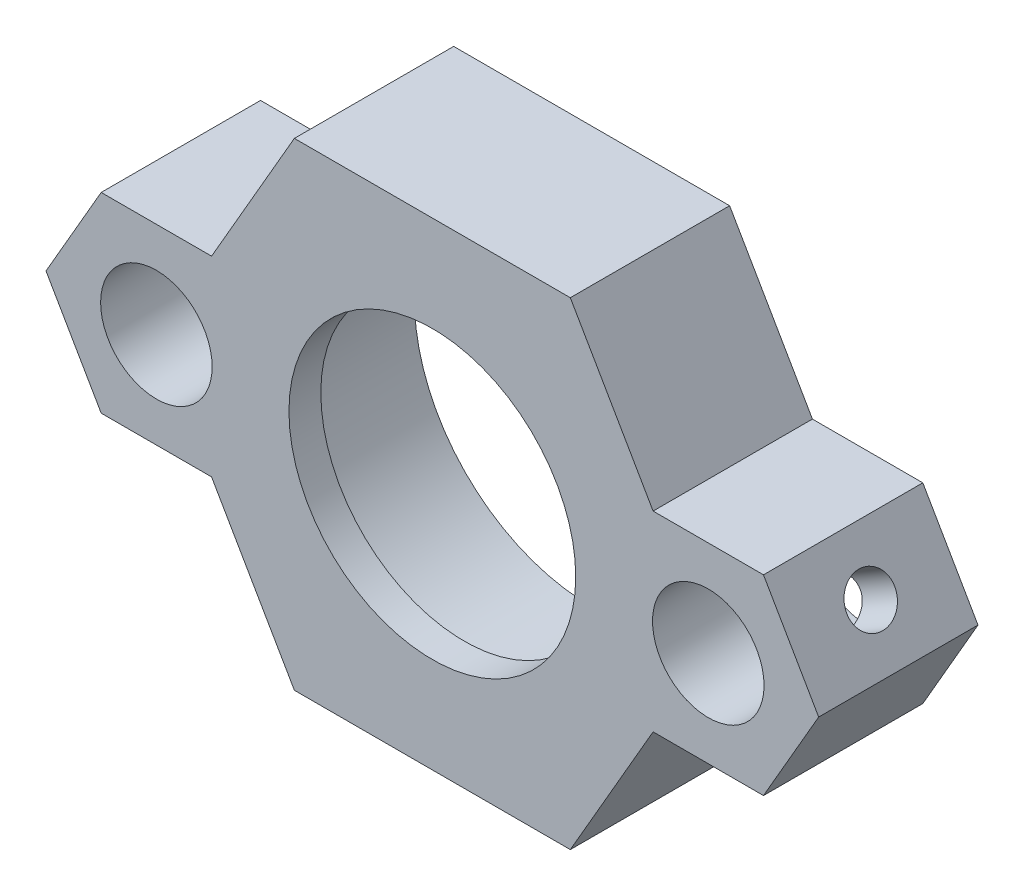
SolidWorks part; units mm, degrees
ref_plane "Front Plane" through (0, 0, 0) normal (0, 0, 1) x (1, 0, 0)
ref_plane "Top Plane" through (0, 0, 0) normal (0, 1, 0) x (1, 0, 0)
ref_plane "Right Plane" through (0, 0, 0) normal (1, 0, 0) x (0, 0, -1)
sketch "Sketch3" plane through (0, 0, 0) normal (0, 0, 1) x (1, 0, 0)
  line L0 (-15, 0) -> (17.3205, 0) construction
  line L1 (17.3205, 0) -> (15.5705, 3.0311) construction
  line L2 (8.6603, 15) -> (-8.6603, 15)
  line L3 (-8.6603, 15) -> (-13.8564, 6)
  line L4 (-13.8564, -6) -> (-8.6603, -15)
  line L5 (-8.6603, -15) -> (8.6603, -15)
  line L6 (8.6603, -15) -> (13.8564, -6)
  line L7 (0, 15) -> (0, -15) construction
  line L8 (24.2487, 0) -> (20.7846, 6)
  line L9 (20.7846, 6) -> (13.8564, 6)
  line L10 (12.1244, 3) -> (11.064, 1.1634) construction
  line L11 (11.064, -1.1634) -> (12.1244, -3) construction
  line L12 (13.8564, -6) -> (20.7846, -6)
  line L13 (20.7846, -6) -> (24.2487, 0)
  line L14 (-20.7846, -6) -> (-24.2487, 0)
  line L15 (-13.8564, -6) -> (-20.7846, -6)
  line L16 (-11.064, -1.1634) -> (-13.8564, -6) construction
  line L17 (-11.064, 1.1634) -> (-10.3923, 0) construction
  line L18 (-20.7846, 6) -> (-13.8564, 6)
  line L19 (-24.2487, 0) -> (-20.7846, 6)
  line L20 (-15.5705, 3.0311) -> (-17.3205, 0) construction
  line L21 (-17.3205, 0) -> (-15, 0) construction
  line L22 (-17.3205, 0) -> (-15.5705, -3.0311) construction
  line L23 (-13.8564, 6) -> (-15.5705, 3.0311) construction
  line L24 (-15.5705, -3.0311) -> (-13.8564, -6) construction
  line L25 (15.5705, 3.0311) -> (14.3205, 5.1962) construction
  line L26 (13.8564, 6) -> (8.6603, 15)
  line L27 (15.5705, -3.0311) -> (17.3205, 0) construction
  line L28 (14.3205, -5.1962) -> (15.5705, -3.0311) construction
  line L29 (13.8564, -6) -> (14.3205, -5.1962) construction
  line L30 (14.3205, 5.1962) -> (13.8564, 6) construction
  line L31 (-13.8564, 6) -> (-11.064, 1.1634) construction
  line L32 (-10.3923, 0) -> (-11.064, -1.1634) construction
  line L33 (12.1244, -3) -> (13.8564, -6) construction
  line L34 (10.3923, 0) -> (11.064, -1.1634) construction
  line L35 (11.064, 1.1634) -> (10.3923, 0) construction
  line L36 (13.8564, 6) -> (12.1244, 3) construction
  circle A0 centre (0, 0) radius 11.125
  circle A1 centre (0, 0) radius 15 construction
  circle A2 centre (17.3205, 0) radius 3.5
  circle A3 centre (17.3205, 0) radius 6 construction
  circle A4 centre (-17.3205, 0) radius 3.5
  dimension "D1" = 22.25
  dimension "D3" = 7
  dimension "D2" = 30
  dimension "D4" = 12
extrude "Boss-Extrude1" add sketch "Sketch3" along normal blind 8
sketch "Sketch4" plane through (0, 0, 8) normal (0, 0, 1) x (1, 0, 0)
  line L0 (-8.6603, 15) -> (-13.8564, 6)
  line L1 (-13.8564, 6) -> (-20.7846, 6)
  line L2 (-20.7846, 6) -> (-24.2487, 0)
  line L3 (-24.2487, 0) -> (-20.7846, -6)
  line L4 (-20.7846, -6) -> (-13.8564, -6)
  line L5 (-13.8564, -6) -> (-8.6603, -15)
  line L6 (-8.6603, -15) -> (8.6603, -15)
  line L7 (8.6603, -15) -> (13.8564, -6)
  line L8 (13.8564, -6) -> (20.7846, -6)
  line L9 (20.7846, -6) -> (24.2487, 0)
  line L10 (24.2487, 0) -> (20.7846, 6)
  line L11 (20.7846, 6) -> (13.8564, 6)
  line L12 (13.8564, 6) -> (8.6603, 15)
  line L13 (8.6603, 15) -> (-8.6603, 15)
  circle A0 centre (0, 0) radius 9
  circle A1 centre (-17.3205, 0) radius 3.5
  circle A2 centre (17.3205, 0) radius 3.5
  circle A3 centre (-17.3205, 0) radius 3.5 construction
  circle A4 centre (17.3205, 0) radius 3.5 construction
  dimension "D1" = 18
extrude "Boss-Extrude3" add sketch "Sketch4" along normal blind 2
sketch "Sketch5" plane through (-18.1865, 10.5, 0) normal (-0.866, 0.5, 0) x (0, 0, 1)
  line L0 (5, -5.1962) -> (5, -12.1244) construction
  line L1 (10, -5.1962) -> (0, -5.1962) construction
  line L2 (10, -12.1244) -> (0, -12.1244) construction
  line L3 (0, -8.6603) -> (10, -8.6603) construction
  line L4 (0, -5.1962) -> (0, -12.1244) construction
  circle A0 centre (5, -8.6603) radius 1.5
  dimension "D1" = 3
extrude "Cut-Extrude1" cut sketch "Sketch5" against normal up to surface (2.8377 mm away) up to face at (-20.8205, 0, 0)
sketch "Sketch6" plane through (18.1865, 10.5, 0) normal (0.866, 0.5, 0) x (0, 0, -1)
  line L0 (-5, -5.1962) -> (-5, -12.1244) construction
  line L1 (-10, -5.1962) -> (0, -5.1962) construction
  line L2 (-10, -12.1244) -> (0, -12.1244) construction
  line L3 (-10, -8.6603) -> (0, -8.6603) construction
  line L4 (-10, -12.1244) -> (-10, -5.1962) construction
  line L5 (0, -12.1244) -> (0, -5.1962) construction
  circle A0 centre (-5, -8.6603) radius 1.5
  dimension "D1" = 3
extrude "Cut-Extrude2" cut sketch "Sketch6" against normal up to surface (2.8377 mm away) up to face at (20.8205, 0, 0)
